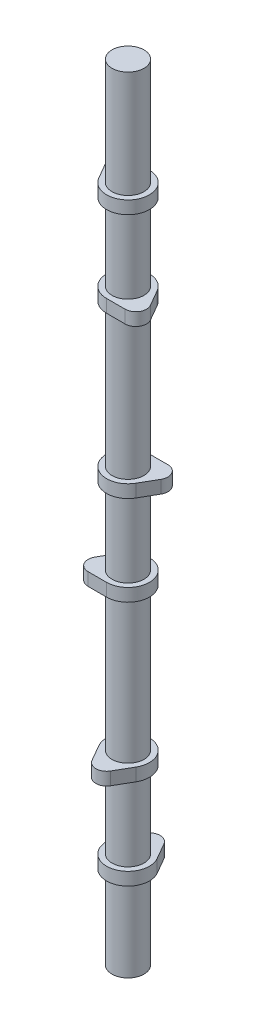
SolidWorks part; units mm, degrees
ref_plane "Front Plane" through (0, 0, 0) normal (0, 0, 1) x (1, 0, 0)
ref_plane "Top Plane" through (0, 0, 0) normal (0, 1, 0) x (1, 0, 0)
ref_plane "Right Plane" through (0, 0, 0) normal (1, 0, 0) x (0, 0, -1)
sketch "Sketch1" plane through (0, 0, 0) normal (0, 1, 0) x (1, 0, 0)
  line L0 (-5.4993, 15.875) -> (-10.9985, 6.35)
  line L1 (5.4993, 15.875) -> (10.9985, 6.35)
  arc A0 (-10.9985, 6.35) -> (10.9985, 6.35) centre (0, 0) ccw
  arc A1 (5.4993, 15.875) -> (-5.4993, 15.875) centre (0, 12.7) ccw
  dimension "D1" = 12.7
  dimension "D2" = 12.7
  dimension "D3" = 25.4
extrude "Boss-Extrude1" add sketch "Sketch1" along normal blind 7.62
ref_axis "Axis1" through (0, 97.6159, 0) along (0, -1, 0)
pattern_linear "LPattern1" count 2 spacing 53.34 along (0, 1, 0) of bodies 101
move or copy body "Body-Move/Copy1" bodies to move or copy 102 copy no rotation origin (0, 0, 0) rotation axis (0, 1, 0) rotation angle 180
pattern_linear "LPattern2" count 3 spacing 146.05 along (0, 1, 0) of bodies 101 103
move or copy body "Body-Move/Copy2" bodies to move or copy 104 106 copy no rotation origin (0, 0, 0) rotation axis (0, 1, 0) rotation angle 120
move or copy body "Body-Move/Copy3" bodies to move or copy 105 107 copy no rotation origin (0, 0, 0) rotation axis (0, -1, 0) rotation angle 120
sketch "Sketch2" plane through (0, 0, 0) normal (0, 1, 0) x (1, 0, 0)
  circle A0 centre (0, 0) radius 9.5
  dimension "D1" = 19
extrude "Boss-Extrude2" add sketch "Sketch2" along normal blind 466.09 from offset 49.53 offset against normal yes
